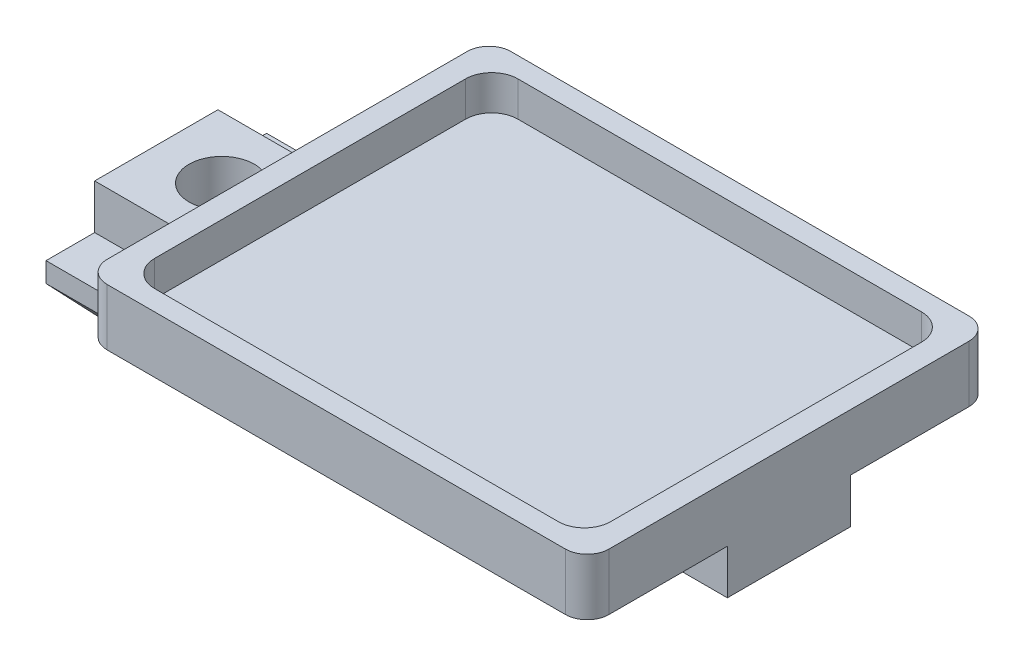
SolidWorks part; units mm, degrees
ref_plane "Front Plane" through (0, 0, 0) normal (0, 0, 1) x (1, 0, 0)
ref_plane "Top Plane" through (0, 0, 0) normal (0, 1, 0) x (1, 0, 0)
ref_plane "Right Plane" through (0, 0, 0) normal (1, 0, 0) x (0, 0, -1)
sketch "Sketch1" plane through (0, 0, 0) normal (0, 1, 0) x (1, 0, 0)
  line L1 (-11.5, -9.25) -> (11.5, -9.25)
  line L2 (-11.5, -9.25) -> (-11.5, 9.25)
  line L3 (-11.5, 9.25) -> (11.5, 9.25)
  line L4 (11.5, -9.25) -> (11.5, 9.25)
  line L5 (-11.5, -9.25) -> (11.5, 9.25) construction
  line L6 (-11.5, 9.25) -> (11.5, -9.25) construction
  point P0 (0, 0)
  dimension "D1" = 23
  dimension "D2" = 18.5
extrude "Boss-Extrude1" add sketch "Sketch1" along normal blind 1
fillet "Fillet1" radius 1 4 edges at (-11.5, 0.5, -9.25) (-11.5, 0.5, 9.25) (11.5, 0.5, -9.25) (11.5, 0.5, 9.25)
sketch "Sketch2" plane through (0, 1, 0) normal (0, 1, 0) x (1, 0, 0)
  line L4 (10.5, 9.25) -> (-10.5, 9.25)
  line L5 (-11.5, 8.25) -> (-11.5, -8.25)
  line L6 (-10.5, -9.25) -> (10.5, -9.25)
  line L7 (11.5, -8.25) -> (11.5, 8.25)
  line L8 (10.5, 9.25) -> (-10.5, 9.25)
  line L9 (-11.5, 8.25) -> (-11.5, -8.25)
  line L10 (-10.5, -9.25) -> (10.5, -9.25)
  line L11 (11.5, -8.25) -> (11.5, 8.25)
  line L45 (9.25, 8.325) -> (-9.25, 8.325)
  line L46 (10.45, -7.125) -> (10.45, 7.125)
  line L47 (-9.25, -8.325) -> (9.25, -8.325)
  line L48 (-10.45, 7.125) -> (-10.45, -7.125)
  arc A4 (-10.5, 9.25) -> (-11.5, 8.25) centre (-10.5, 8.25) ccw
  arc A5 (-11.5, -8.25) -> (-10.5, -9.25) centre (-10.5, -8.25) ccw
  arc A6 (10.5, -9.25) -> (11.5, -8.25) centre (10.5, -8.25) ccw
  arc A7 (11.5, 8.25) -> (10.5, 9.25) centre (10.5, 8.25) ccw
  arc A8 (-10.5, 9.25) -> (-11.5, 8.25) centre (-10.5, 8.25) ccw
  arc A9 (-11.5, -8.25) -> (-10.5, -9.25) centre (-10.5, -8.25) ccw
  arc A10 (10.5, -9.25) -> (11.5, -8.25) centre (10.5, -8.25) ccw
  arc A11 (11.5, 8.25) -> (10.5, 9.25) centre (10.5, 8.25) ccw
  arc A40 (-9.25, 8.325) -> (-10.45, 7.125) centre (-9.25, 7.125) ccw
  arc A41 (10.45, 7.125) -> (9.25, 8.325) centre (9.25, 7.125) ccw
  arc A42 (9.25, -8.325) -> (10.45, -7.125) centre (9.25, -7.125) ccw
  arc A43 (-10.45, -7.125) -> (-9.25, -8.325) centre (-9.25, -7.125) ccw
  dimension "D1" = 0
extrude "Boss-Extrude2" add sketch "Sketch2" along normal blind 1.6
sketch "Sketch3" plane through (0, 0, 0) normal (1, 0, 0) x (0, 0, -1)
  line L9 (-3.075, -0.4342) -> (-3.075, -1.8) construction
  line L10 (-3.075, -1.8) -> (-5.3047, -1.8) construction
  line L11 (-5.3047, -1.8) -> (-5.3047, -3.0596) construction
  line L12 (-5.3047, -3.0596) -> (-2.4047, -6.1) construction
  line L13 (-2.4047, -6.1) -> (2.4047, -6.1) construction
  line L14 (3.075, -1.8) -> (3.075, -0.5209) construction
  line L15 (2.4047, -6.1) -> (5.3047, -3.2) construction
  line L16 (5.3047, -1.8) -> (3.075, -1.8) construction
  line L17 (5.3047, -3.2) -> (5.3047, -1.8) construction
  line L18 (-3.075, -0.4342) -> (-3.075, 0) construction
  line L19 (-8.25, 0) -> (8.25, 0) construction
  line L20 (3.075, -0.5209) -> (3.075, 0) construction
  line L21 (-2.825, -0.4342) -> (-2.825, 0)
  line L22 (-2.825, -0.4342) -> (-2.825, -2.05)
  line L23 (-2.825, -2.05) -> (-5.0547, -2.05)
  line L24 (-5.0547, -2.05) -> (-5.0547, -2.9595)
  line L25 (-5.0547, -2.9595) -> (-2.2976, -5.85)
  line L26 (-2.2976, -5.85) -> (2.3011, -5.85)
  line L27 (2.3011, -5.85) -> (5.0547, -3.0964)
  line L28 (5.0547, -3.0964) -> (5.0547, -2.05)
  line L29 (5.0547, -2.05) -> (2.825, -2.05)
  line L30 (2.825, -2.05) -> (2.825, -0.5209)
  line L31 (2.825, -0.5209) -> (2.825, 0)
  line L32 (-2.825, 0) -> (2.825, 0)
  dimension "D1" = 0.25
extrude "Boss-Extrude3" add sketch "Sketch3" against normal blind 17.5
sketch "Sketch4" plane through (0, 0, 0) normal (1, 0, 0) x (0, 0, -1)
  line L0 (-2.825, -2.05) -> (2.825, -2.05)
  line L10 (-2.825, 0) -> (-2.825, -2.05)
  line L11 (-2.825, -2.05) -> (-5.0547, -2.05)
  line L12 (-5.0547, -2.05) -> (-5.0547, -2.9595)
  line L13 (-5.0547, -2.9595) -> (-2.2976, -5.85)
  line L14 (-2.2976, -5.85) -> (2.3011, -5.85)
  line L15 (2.3011, -5.85) -> (5.0547, -3.0964)
  line L16 (5.0547, -3.0964) -> (5.0547, -2.05)
  line L17 (5.0547, -2.05) -> (2.825, -2.05)
  line L18 (2.825, -2.05) -> (2.825, 0)
  line L19 (2.825, 0) -> (-2.825, 0)
  line L20 (-2.825, 0) -> (-2.825, -2.05)
  line L28 (2.825, -2.05) -> (2.825, 0)
  line L29 (2.825, 0) -> (-2.825, 0)
  dimension "D1" = 0
extrude "Boss-Extrude4" add sketch "Sketch4" along normal up to surface (11.5 mm away) up to face at (11.5, 1.3, 0)
fillet "Fillet2" radius 6 1 edges at (0, -5.85, -0.0017)
sketch "Sketch5" plane through (0, 0, 0) normal (0, 1, 0) x (1, 0, 0)
  line L0 (-14.5, 2.825) -> (-14.5, 0) construction
  line L1 (-17.5, 2.825) -> (-11.5, 2.825) construction
  line L2 (-17.5, 0) -> (-14.5, 0) construction
  line L3 (-17.5, 2.825) -> (-17.5, -2.825) construction
  circle A0 centre (-14.5, 0) radius 1.5
extrude "Cut-Extrude1" cut sketch "Sketch5" against normal blind 9
sketch "Sketch6" plane through (0, -5.85, 0) normal (0, -1, 0) x (1, 0, 0)
  circle A0 centre (-14.5, 0) radius 1.85
  circle A1 centre (-14.5, 0) radius 2.085 construction
extrude "Cut-Extrude3" cut sketch "Sketch6" against normal blind 3
